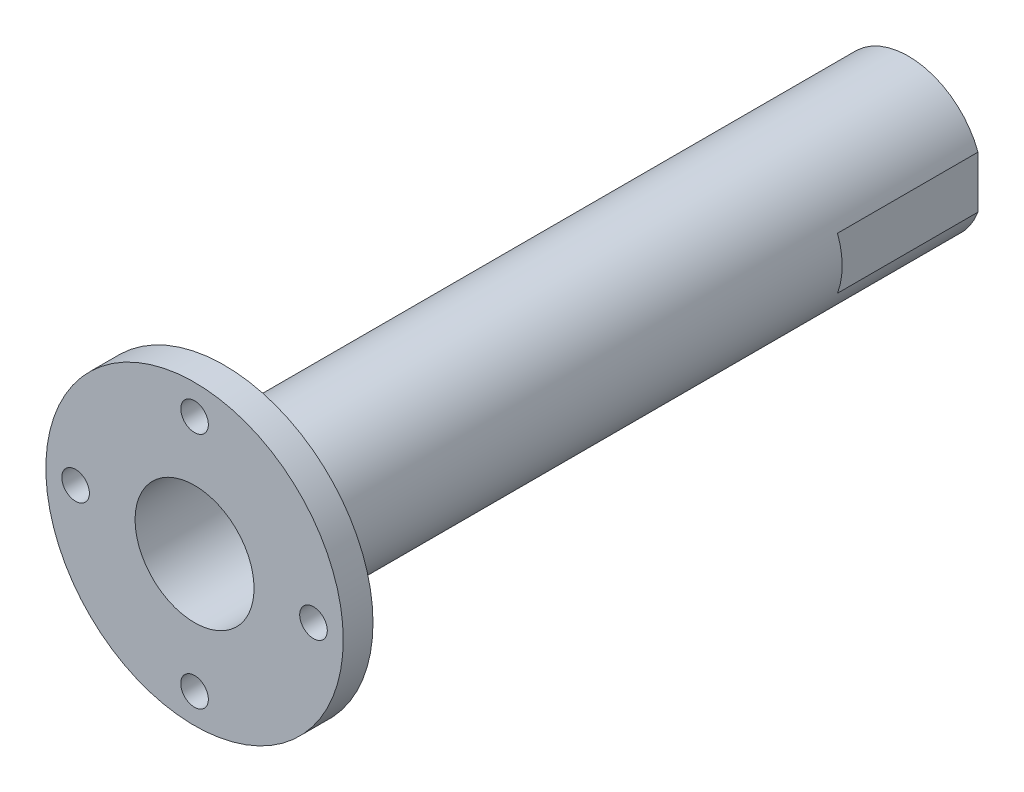
SolidWorks part; units mm, degrees
material "Tin Bearing Bronze"
ref_plane "Front Plane" through (0, 0, 0) normal (0, 0, 1) x (1, 0, 0)
ref_plane "Top Plane" through (0, 0, 0) normal (0, 1, 0) x (1, 0, 0)
ref_plane "Right Plane" through (0, 0, 0) normal (1, 0, 0) x (0, 0, -1)
sketch "Sketch1" plane through (0, 0, 0) normal (0, 0, 1) x (1, 0, 0)
  circle A0 centre (0, 0) radius 6.35
  circle A1 centre (0, 0) radius 7.9375
  dimension "D1" = 15.875
  dimension "D2" = 12.7
extrude "Boss-Extrude1" add sketch "Sketch1" along normal blind 76.2
sketch "Sketch2" plane through (0, 0, 76.2) normal (0, 0, 1) x (1, 0, 0)
  circle A0 centre (0, 0) radius 15.875
  circle A1 centre (0, 0) radius 6.35 construction
  circle A2 centre (0, 0) radius 6.35
  dimension "D1" = 31.75
extrude "Boss-Extrude2" add sketch "Sketch2" against normal blind 3.175
hole_wizard "#4 Clearance Hole1" positions "Sketch4" profile "Sketch5" hole size "#4" standard "ANSI Inch"
sketch "Sketch4" plane through (0, 0, 76.2) normal (0, 0, 1) x (1, 0, 0)
  point P0 (0, 12.7)
  point P2 (0, -12.7)
  point P4 (12.7, 0)
  point P6 (-12.7, 0)
  dimension "D1" = 12.7
  dimension "D2" = 12.7
  dimension "D3" = 12.7
  dimension "D4" = 12.7
sketch "Sketch5" plane through (0, 12.7, 76.2) normal (1, 0, 0) x (0, -1, 0)
  line L0 (0, 0) -> (0, 4.8852)
  line L1 (0, 4.8852) -> (1.4732, 4)
  line L2 (1.4732, 4) -> (1.4732, 0)
  line L5 (1.4732, 0) -> (0, 0)
  line L10 (0, 4.8852) -> (-1.4732, 4) construction
  line L11 (0, -6.35) -> (0, 107.95) construction
  dimension "Hole Dia." = 2.9464
  dimension "Hole Depth" = 4
  dimension "Drill Angle" = 118
sketch "Sketch6" plane through (0, 0, 0) normal (0, 1, 0) x (1, 0, 0)
  line L1 (7.4375, -15) -> (11.5746, -15)
  line L2 (7.4375, -73.025) -> (7.4375, 0)
  line L3 (7.4375, -73.025) -> (7.4375, 0)
  line L4 (7.4375, 0) -> (11.5746, 0)
  line L5 (11.5746, 0) -> (11.5746, -15)
  point P4 (9.5061, 0)
  dimension "D2" = 15
  dimension "D1" = 0.5
extrude "Cut-Extrude1" cut sketch "Sketch6" along normal through all both and the other way through all contours L5 L4 L3 L1 region at (9.5061, 0, 7.5)
